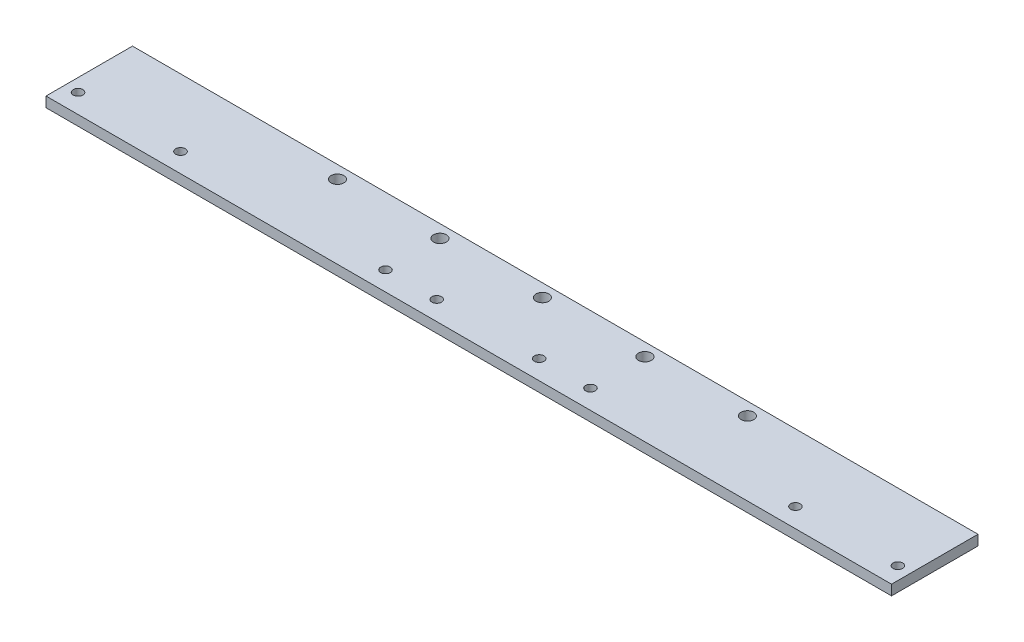
SolidWorks part; units mm, degrees
ref_plane "Front" through (0, 0, 0) normal (0, 0, 1) x (1, 0, 0)
ref_plane "Top" through (0, 0, 0) normal (0, 1, 0) x (1, 0, 0)
ref_plane "Right" through (0, 0, 0) normal (1, 0, 0) x (0, 0, -1)
sketch "Sketch1" plane through (0, 0, 0) normal (0, 1, 0) x (1, 0, 0)
  line L0 (0, 25.5356) -> (0, -1.4644)
  line L3 (0, 25.5356) -> (264, 25.5356)
  line L7 (0, -1.4644) -> (264, -1.4644)
  line L8 (264, -1.4644) -> (264, 25.5356)
  line L9 (264, -1.4644) -> (264, 10.5356)
  line L10 (264, 21.5356) -> (260, 21.5356)
  line L11 (0, 21.5356) -> (4, 21.5356)
  line L12 (4, 21.5356) -> (260, 21.5356)
  line L13 (4, 21.5356) -> (132, 21.5356)
  line L14 (132, 21.5356) -> (260, 21.5356)
  line L15 (264, 10.5356) -> (264, -1.4644)
  line L16 (264, 4.5356) -> (260, 4.5356)
  line L17 (132, 25.5356) -> (132, 23.5356)
  line L18 (4, 21.5356) -> (68, 21.5356)
  line L19 (68, 21.5356) -> (36, 21.5356)
  line L20 (36, 21.5356) -> (36, 4.5356)
  line L21 (196, 21.5356) -> (260, 21.5356)
  line L22 (228, 21.5356) -> (228, 4.5356)
  line L23 (132, 21.5356) -> (132, 4.5356)
  line L24 (132, 21.5356) -> (164, 21.5356)
  circle A0 centre (4, 21.5356) radius 2
  circle A1 centre (260, 21.5356) radius 2
  circle A2 centre (132, 21.5356) radius 2
  circle A3 centre (68, 21.5356) radius 2
  circle A4 centre (196, 21.5356) radius 2
  circle A5 centre (260, 4.5356) radius 1.5
  circle A6 centre (4, 4.5356) radius 1.5
  circle A7 centre (36, 4.5356) radius 1.5
  circle A8 centre (228, 4.5356) radius 1.5
  circle A9 centre (132, 4.5356) radius 1.5
  circle A10 centre (164, 21.5356) radius 2
  circle A11 centre (100, 21.5356) radius 2
  dimension "D5" = 23
  dimension "D6" = 128
  dimension "D9" = 4
  dimension "D10" = 32
  dimension "D1" = 4
  dimension "D2" = 264
  dimension "D3" = 4
  dimension "D4" = 4
  dimension "D7" = 128
  dimension "D8" = 12
extrude "Boss-Extrude1" add sketch "Sketch1" along normal blind 3.175 contours A1 L10 L3 A0 | A1 A0 L10 | A3 L13 A2 L17 L3 L0 L11 A0 | A9 | A0 | A1 region at (65.9183, 0, -23.5857) region at (1, 0, -18.8856) region at (198.0817, 0, -23.5857)
sketch "Sketch2" plane through (0, 3.175, 0) normal (0, 1, 0) x (1, 0, 0)
  line L0 (37.5, 4.5356) -> (228, 4.5356)
  line L1 (132, 21.5356) -> (132, 4.5356)
  line L2 (132, 4.5356) -> (148, 4.5356)
  line L3 (148, 4.5356) -> (116, 4.5356)
  line L4 (116, 4.5356) -> (100, 4.5356)
  line L5 (148, 4.5356) -> (164, 4.5356)
  circle A0 centre (36, 4.5356) radius 1.5 construction
  circle A1 centre (116, 4.5356) radius 1.5
  circle A2 centre (148, 4.5356) radius 1.5
  circle A3 centre (100, 4.5356) radius 1.5
  circle A4 centre (164, 4.5356) radius 1.5
  dimension "D3" = 16
  dimension "D1" = 16
  dimension "D2" = 16
  dimension "D4" = 16
extrude "Cut-Extrude1" cut sketch "Sketch2" against normal blind 10 contours A3 | A1 | A2 | A4
